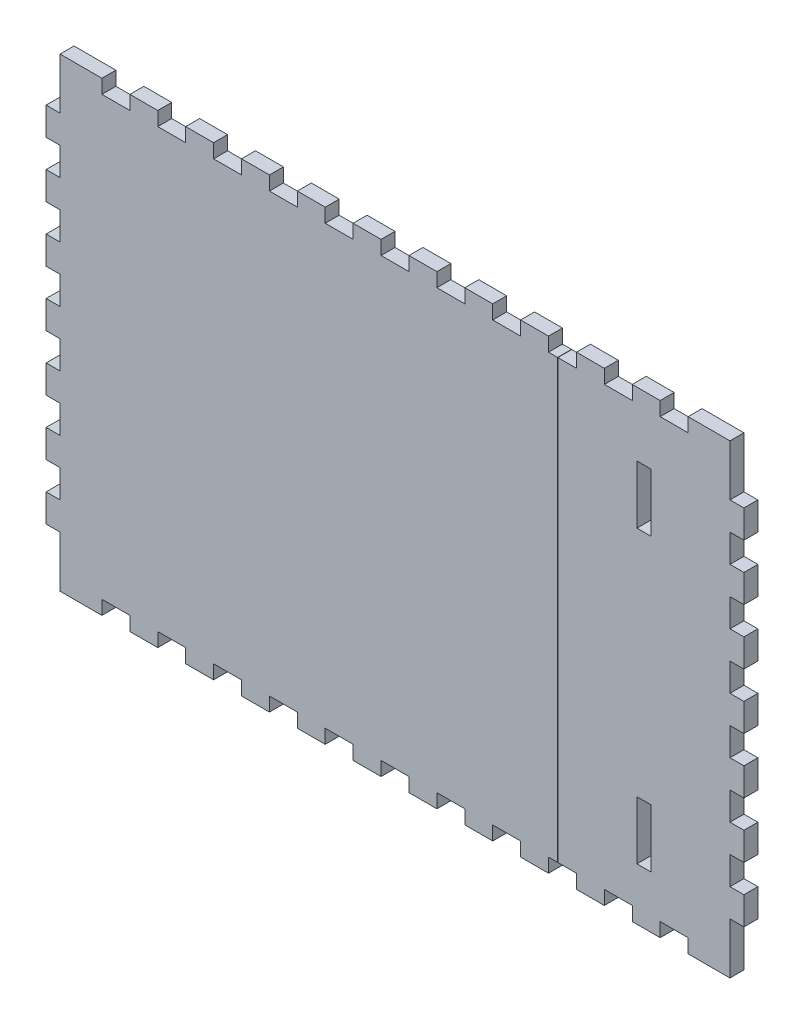
SolidWorks part; units mm, degrees
ref_plane "Front Plane" through (0, 0, 0) normal (0, 0, 1) x (1, 0, 0)
ref_plane "Top Plane" through (0, 0, 0) normal (0, 1, 0) x (1, 0, 0)
ref_plane "Right Plane" through (0, 0, 0) normal (1, 0, 0) x (0, 0, -1)
sketch "Model" plane through (0, 0, 0) normal (0, 0, 1) x (1, 0, 0)
  line L0 (209, 203) -> (209, 181)
  line L1 (209, 181) -> (203, 181)
  line L2 (203, 181) -> (203, 169)
  line L3 (203, 169) -> (209, 169)
  line L4 (209, 169) -> (209, 157)
  line L5 (209, 157) -> (203, 157)
  line L6 (203, 157) -> (203, 145)
  line L7 (203, 145) -> (209, 145)
  line L8 (209, 145) -> (209, 133)
  line L9 (209, 133) -> (203, 133)
  line L10 (203, 133) -> (203, 121)
  line L11 (203, 121) -> (209, 121)
  line L12 (209, 121) -> (209, 109)
  line L13 (209, 109) -> (203, 109)
  line L14 (203, 109) -> (203, 97)
  line L15 (203, 97) -> (209, 97)
  line L16 (209, 97) -> (209, 85)
  line L17 (209, 85) -> (203, 85)
  line L18 (203, 85) -> (203, 73)
  line L19 (203, 73) -> (209, 73)
  line L20 (209, 73) -> (209, 61)
  line L21 (209, 61) -> (203, 61)
  line L22 (203, 61) -> (203, 49)
  line L23 (203, 49) -> (209, 49)
  line L24 (209, 49) -> (209, 37)
  line L25 (209, 37) -> (203, 37)
  line L26 (203, 37) -> (203, 25)
  line L27 (203, 25) -> (209, 25)
  line L28 (209, 25) -> (209, 13)
  line L29 (209, 13) -> (209, 3)
  line L30 (209, 3) -> (227, 3)
  line L31 (227, 3) -> (227, 9)
  line L32 (227, 9) -> (239, 9)
  line L33 (239, 9) -> (239, 3)
  line L34 (239, 3) -> (251, 3)
  line L35 (251, 3) -> (251, 9)
  line L36 (251, 9) -> (263, 9)
  line L37 (263, 9) -> (263, 3)
  line L38 (263, 3) -> (275, 3)
  line L39 (275, 3) -> (275, 9)
  line L40 (275, 9) -> (287, 9)
  line L41 (287, 9) -> (287, 3)
  line L42 (287, 3) -> (299, 3)
  line L43 (299, 3) -> (299, 9)
  line L44 (299, 9) -> (311, 9)
  line L45 (311, 9) -> (311, 3)
  line L46 (311, 3) -> (323, 3)
  line L47 (323, 3) -> (323, 9)
  line L48 (323, 9) -> (335, 9)
  line L49 (335, 9) -> (335, 3)
  line L50 (335, 3) -> (347, 3)
  line L51 (347, 3) -> (347, 9)
  line L52 (347, 9) -> (359, 9)
  line L53 (359, 9) -> (359, 3)
  line L54 (359, 3) -> (371, 3)
  line L55 (371, 3) -> (371, 9)
  line L56 (371, 9) -> (383, 9)
  line L57 (383, 9) -> (383, 3)
  line L58 (383, 3) -> (395, 3)
  line L59 (395, 3) -> (395, 9)
  line L60 (395, 9) -> (407, 9)
  line L61 (407, 9) -> (407, 3)
  line L62 (407, 3) -> (419, 3)
  line L63 (419, 3) -> (419, 9)
  line L64 (419, 9) -> (431, 9)
  line L65 (431, 9) -> (431, 3)
  line L66 (431, 3) -> (443, 3)
  line L67 (443, 3) -> (443, 9)
  line L68 (443, 9) -> (455, 9)
  line L69 (455, 9) -> (455, 3)
  line L70 (455, 3) -> (467, 3)
  line L71 (467, 3) -> (467, 9)
  line L72 (467, 9) -> (479, 9)
  line L73 (479, 9) -> (479, 3)
  line L74 (479, 3) -> (491, 3)
  line L75 (491, 3) -> (497, 3)
  line L76 (497, 3) -> (497, 25)
  line L77 (497, 25) -> (503, 25)
  line L78 (503, 25) -> (503, 37)
  line L79 (503, 37) -> (497, 37)
  line L80 (497, 37) -> (497, 49)
  line L81 (497, 49) -> (503, 49)
  line L82 (503, 49) -> (503, 61)
  line L83 (503, 61) -> (497, 61)
  line L84 (497, 61) -> (497, 73)
  line L85 (497, 73) -> (503, 73)
  line L86 (503, 73) -> (503, 85)
  line L87 (503, 85) -> (497, 85)
  line L88 (497, 85) -> (497, 97)
  line L89 (497, 97) -> (503, 97)
  line L90 (503, 97) -> (503, 109)
  line L91 (503, 109) -> (497, 109)
  line L92 (497, 109) -> (497, 121)
  line L93 (497, 121) -> (503, 121)
  line L94 (503, 121) -> (503, 133)
  line L95 (503, 133) -> (497, 133)
  line L96 (497, 133) -> (497, 145)
  line L97 (497, 145) -> (503, 145)
  line L98 (503, 145) -> (503, 157)
  line L99 (503, 157) -> (497, 157)
  line L100 (497, 157) -> (497, 169)
  line L101 (497, 169) -> (503, 169)
  line L102 (503, 169) -> (503, 181)
  line L103 (503, 181) -> (497, 181)
  line L104 (497, 181) -> (497, 193)
  line L105 (497, 193) -> (497, 203)
  line L106 (497, 203) -> (479, 203)
  line L107 (479, 203) -> (479, 197)
  line L108 (479, 197) -> (467, 197)
  line L109 (467, 197) -> (467, 203)
  line L110 (467, 203) -> (455, 203)
  line L111 (455, 203) -> (455, 197)
  line L112 (455, 197) -> (443, 197)
  line L113 (443, 197) -> (443, 203)
  line L114 (443, 203) -> (431, 203)
  line L115 (431, 203) -> (431, 197)
  line L116 (431, 197) -> (419, 197)
  line L117 (419, 197) -> (419, 203)
  line L118 (419, 203) -> (407, 203)
  line L119 (407, 203) -> (407, 197)
  line L120 (407, 197) -> (395, 197)
  line L121 (395, 197) -> (395, 203)
  line L122 (395, 203) -> (383, 203)
  line L123 (383, 203) -> (383, 197)
  line L124 (383, 197) -> (371, 197)
  line L125 (371, 197) -> (371, 203)
  line L126 (371, 203) -> (359, 203)
  line L127 (359, 203) -> (359, 197)
  line L128 (359, 197) -> (347, 197)
  line L129 (347, 197) -> (347, 203)
  line L130 (347, 203) -> (335, 203)
  line L131 (335, 203) -> (335, 197)
  line L132 (335, 197) -> (323, 197)
  line L133 (323, 197) -> (323, 203)
  line L134 (323, 203) -> (311, 203)
  line L135 (311, 203) -> (311, 197)
  line L136 (311, 197) -> (299, 197)
  line L137 (299, 197) -> (299, 203)
  line L138 (299, 203) -> (287, 203)
  line L139 (287, 203) -> (287, 197)
  line L140 (287, 197) -> (275, 197)
  line L141 (275, 197) -> (275, 203)
  line L142 (275, 203) -> (263, 203)
  line L143 (263, 203) -> (263, 197)
  line L144 (263, 197) -> (251, 197)
  line L145 (251, 197) -> (251, 203)
  line L146 (251, 203) -> (239, 203)
  line L147 (239, 203) -> (239, 197)
  line L148 (239, 197) -> (227, 197)
  line L149 (227, 197) -> (227, 203)
  line L150 (227, 203) -> (215, 203)
  line L151 (215, 203) -> (209, 203)
extrude "Boss-Extrude1" add sketch "Model" along normal blind 6
sketch "Sketch2" plane through (0, 0, 6) normal (0, 0, 1) x (1, 0, 0)
  line L0 (497, 181) -> (497, 203) construction
  line L1 (422.9, 218.155) -> (423, 218.155)
  line L2 (422.9, 218.155) -> (422.9, -17.155)
  line L3 (422.9, -17.155) -> (423, -17.155)
  line L4 (423, 218.155) -> (423, -17.155)
  line L5 (423, 100.5) -> (503, 100.5)
  line L6 (503, 97) -> (503, 109) construction
  line L7 (457, 163) -> (423, 163)
  line L9 (463, 163) -> (497, 163)
  line L11 (497, 157) -> (497, 169) construction
  line L12 (457, 175.5) -> (463, 175.5)
  line L13 (457, 175.5) -> (457, 150.5)
  line L14 (457, 150.5) -> (463, 150.5)
  line L15 (463, 175.5) -> (463, 150.5)
  line L16 (457, 50.5) -> (463, 50.5)
  line L19 (463, 25.5) -> (463, 50.5)
  line L20 (457, 25.5) -> (463, 25.5)
  line L21 (457, 25.5) -> (457, 50.5)
  dimension "D1" = 0.1
  dimension "D2" = 74
  dimension "D3" = 6
  dimension "D4" = 25
  dimension "D5" = 50
extrude "Cut-Extrude1" cut sketch "Sketch2" against normal blind 6 contours L21 L20 L19 L16 | L4 L1 L2 L3 | L13 L14 L15 L12 region at (422.95, 100.5, 6) region at (460, 38, 6)
sketch "Sketch3" plane through (0, 0, 6) normal (0, 0, 1) x (1, 0, 0)
